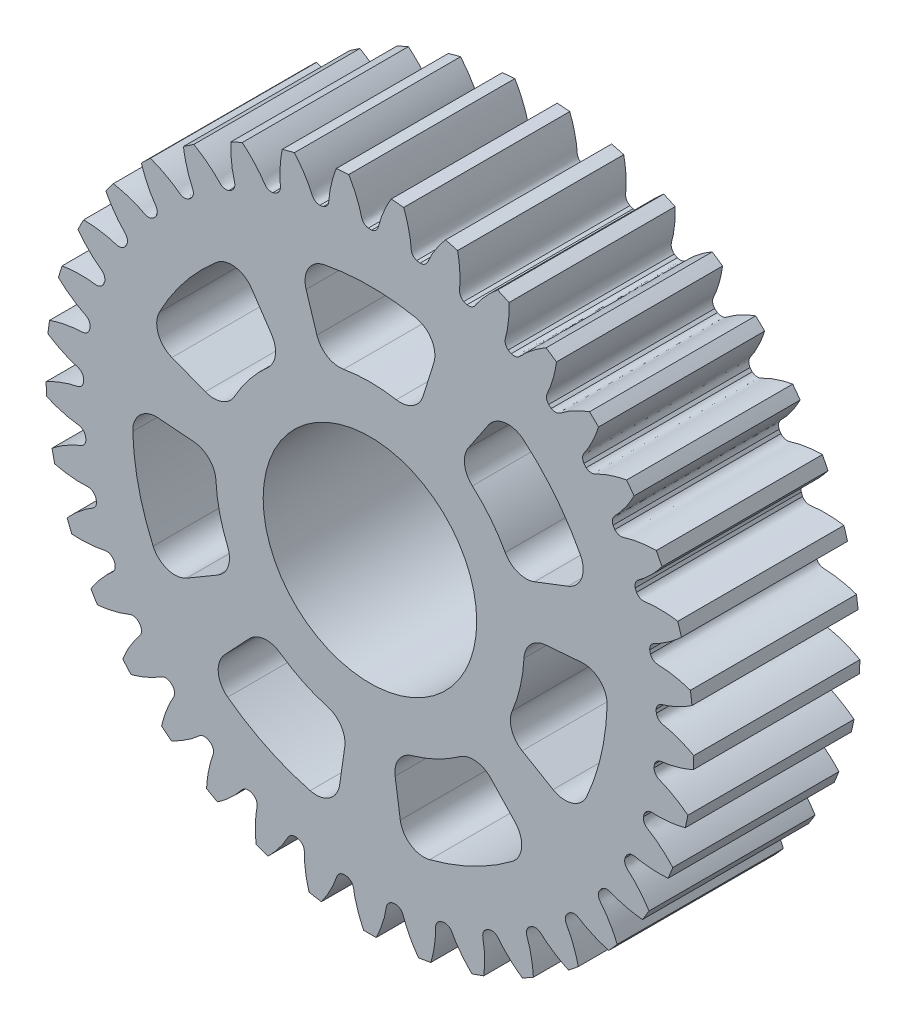
SolidWorks part; units mm, degrees
material "普通碳钢"
ref_plane "前视基准面" through (0, 0, 0) normal (0, 0, 1) x (1, 0, 0)
ref_plane "上视基准面" through (0, 0, 0) normal (0, 1, 0) x (1, 0, 0)
ref_plane "右视基准面" through (0, 0, 0) normal (1, 0, 0) x (0, 0, -1)
sketch "草图1" plane through (0, 0, 0) normal (0, 0, 1) x (1, 0, 0)
  circle A0 centre (0, 0) radius 13.65
extrude "凸台-拉伸1" add sketch "草图1" along normal blind 7
ref_axis "基准轴1" through (0, 0, -0.35) along (0, 0, 1)
sketch "草图2" plane through (0, 0, 0) normal (0, 0, 1) x (1, 0, 0)
  line L0 (0, 0) -> (0, 13.65) construction
  circle A0 centre (0, 0) radius 13.65 construction
  arc A1 (0.0725, 12.0748) -> (-0.0725, 12.0748) centre (0, 0) ccw
  arc A2 (2.4239, 15.4494) -> (-2.4239, 15.4494) centre (0, 0) ccw
  spline S0 degree 3 poles (0.0725, 12.0748) (0.3264, 12.1335) (0.3507, 12.3259) (0.4066, 12.5302) (0.4241, 12.5902) (0.4444, 12.6546) (0.4675, 12.7231) (0.4936, 12.7958) (0.5229, 12.8724) (0.5555, 12.953) (0.5917, 13.0373) (0.6315, 13.1254) (0.6752, 13.217) (0.723, 13.3121) (0.7748, 13.4106) (0.831, 13.5122) (0.8916, 13.6169) (0.9569, 13.7246) (1.0269, 13.835) (1.1017, 13.9481) (1.1816, 14.0636) (1.2666, 14.1815) (1.3569, 14.3015) (1.4526, 14.4236) (1.5538, 14.5475) (1.6606, 14.673) (1.7731, 14.8) (1.8914, 14.9283) (2.0156, 15.0578) (2.1915, 15.2339) (2.3292, 15.3637) (2.4239, 15.4494) knots 0 0 0 0 0.1237 0.137556 0.152582 0.168775 0.186138 0.204669 0.224368 0.245237 0.267273 0.290479 0.314853 0.340396 0.367107 0.394987 0.424036 0.454253 0.485639 0.518193 0.551916 0.586808 0.622869 0.660098 0.698495 0.738061 0.778796 0.8207 0.863772 0.908013 1 1 1 1
  spline S1 degree 3 poles (-0.0725, 12.0748) (-0.3264, 12.1335) (-0.3507, 12.3259) (-0.4066, 12.5302) (-0.4241, 12.5902) (-0.4444, 12.6546) (-0.4675, 12.7231) (-0.4936, 12.7958) (-0.5229, 12.8724) (-0.5555, 12.953) (-0.5917, 13.0373) (-0.6315, 13.1254) (-0.6752, 13.217) (-0.723, 13.3121) (-0.7748, 13.4106) (-0.831, 13.5122) (-0.8916, 13.6169) (-0.9569, 13.7246) (-1.0269, 13.835) (-1.1017, 13.9481) (-1.1816, 14.0636) (-1.2666, 14.1815) (-1.3569, 14.3015) (-1.4526, 14.4236) (-1.5538, 14.5475) (-1.6606, 14.673) (-1.7731, 14.8) (-1.8914, 14.9283) (-2.0156, 15.0578) (-2.1915, 15.2339) (-2.3292, 15.3637) (-2.4239, 15.4494) knots 0 0 0 0 0.1237 0.137556 0.152582 0.168775 0.186138 0.204669 0.224368 0.245237 0.267273 0.290479 0.314853 0.340396 0.367107 0.394987 0.424036 0.454253 0.485639 0.518193 0.551916 0.586808 0.622869 0.660098 0.698495 0.738061 0.778796 0.8207 0.863772 0.908013 1 1 1 1
extrude "切除-拉伸1" cut sketch "草图2" along normal through all
pattern_circular "阵列(圆周)1" count 37 every 9.73 about axis through (0, 0, -0.35) along (0, 0, 1) of "切除-拉伸1"
sketch "草图3" plane through (0, 0, 0) normal (0, 0, 1) x (1, 0, 0)
  circle A0 centre (0, 0) radius 12.95 construction
  dimension "Dn" = 25.9
sketch "草图4" plane through (0, 0, 7) normal (0, 0, 1) x (1, 0, 0)
  circle A0 centre (0, 0) radius 4.5
  dimension "D1" = 9
extrude "切除-拉伸2" cut sketch "草图4" against normal through all and the other way through all
sketch "草图5" plane through (0, 0, 7) normal (0, 0, 1) x (1, 0, 0)
  line L0 (-3.0071, 9.5372) -> (0, 0) construction
  line L1 (0, 0) -> (3.0071, 9.5372) construction
  line L2 (-3.0071, 9.5372) -> (-1.9546, 6.1992)
  line L3 (1.9546, 6.1992) -> (3.0071, 9.5372)
  line L4 (0, 10) -> (0, 0) construction
  line L5 (5.5816, 8.2973) -> (3.628, 5.3933)
  line L6 (6.0654, 2.337) -> (9.3313, 3.5953)
  line L7 (9.9672, 0.8094) -> (6.4787, 0.5261)
  line L8 (5.6088, -3.285) -> (8.6289, -5.0539)
  line L9 (6.8473, -7.288) -> (4.4507, -4.7372)
  line L10 (0.9287, -6.4333) -> (1.4288, -9.8974)
  line L11 (-1.4288, -9.8974) -> (-0.9287, -6.4333)
  line L12 (-4.4507, -4.7372) -> (-6.8473, -7.288)
  line L13 (-8.6289, -5.0539) -> (-5.6088, -3.285)
  line L14 (-6.4787, 0.5261) -> (-9.9672, 0.8094)
  line L15 (-9.3313, 3.5953) -> (-6.0654, 2.337)
  line L16 (-3.628, 5.3933) -> (-5.5816, 8.2973)
  arc A2 (-3.0071, 9.5372) -> (3.0071, 9.5372) centre (0, 0) cw
  arc A3 (1.9546, 6.1992) -> (-1.9546, 6.1992) centre (0, 0) ccw
  arc A4 (5.5816, 8.2973) -> (9.3313, 3.5953) centre (0, 0) cw
  arc A5 (6.0654, 2.337) -> (3.628, 5.3933) centre (0, 0) ccw
  arc A6 (9.9672, 0.8094) -> (8.6289, -5.0539) centre (0, 0) cw
  arc A7 (5.6088, -3.285) -> (6.4787, 0.5261) centre (0, 0) ccw
  arc A8 (6.8473, -7.288) -> (1.4288, -9.8974) centre (0, 0) cw
  arc A9 (0.9287, -6.4333) -> (4.4507, -4.7372) centre (0, 0) ccw
  arc A10 (-1.4288, -9.8974) -> (-6.8473, -7.288) centre (0, 0) cw
  arc A11 (-4.4507, -4.7372) -> (-0.9287, -6.4333) centre (0, 0) ccw
  arc A12 (-8.6289, -5.0539) -> (-9.9672, 0.8094) centre (0, 0) cw
  arc A13 (-6.4787, 0.5261) -> (-5.6088, -3.285) centre (0, 0) ccw
  arc A14 (-9.3313, 3.5953) -> (-5.5816, 8.2973) centre (0, 0) cw
  arc A15 (-3.628, 5.3933) -> (-6.0654, 2.337) centre (0, 0) ccw
  point P27 (0, 0)
  dimension "D1" = 10
  dimension "D2" = 6.5
  dimension "D3" = 35
  dimension "D4" = 7
extrude "切除-拉伸3" cut sketch "草图5" against normal through all
fillet "圆角1" radius 1 28 edges at (1.9546, 6.1992, 3.5) (-1.9546, 6.1992, 3.5) (-3.0071, 9.5372, 3.5) (3.0071, 9.5372, 3.5) (-3.628, 5.3933, 3.5) (-6.0654, 2.337, 3.5) (-9.3313, 3.5953, 3.5) (-4.4507, -4.7372, 3.5) (-0.9287, -6.4333, 3.5) (-1.4288, -9.8974, 3.5) (-6.8473, -7.288, 3.5) (-6.4787, 0.5261, 3.5) (-5.6088, -3.285, 3.5) (-8.6289, -5.0539, 3.5) (-9.9672, 0.8094, 3.5) (6.0654, 2.337, 3.5) (3.628, 5.3933, 3.5) (5.5816, 8.2973, 3.5) (9.3313, 3.5953, 3.5) (5.6088, -3.285, 3.5) (6.4787, 0.5261, 3.5) (9.9672, 0.8094, 3.5) (8.6289, -5.0539, 3.5) (0.9287, -6.4333, 3.5) (4.4507, -4.7372, 3.5) (6.8473, -7.288, 3.5) (1.4288, -9.8974, 3.5) (-5.5816, 8.2973, 3.5)
